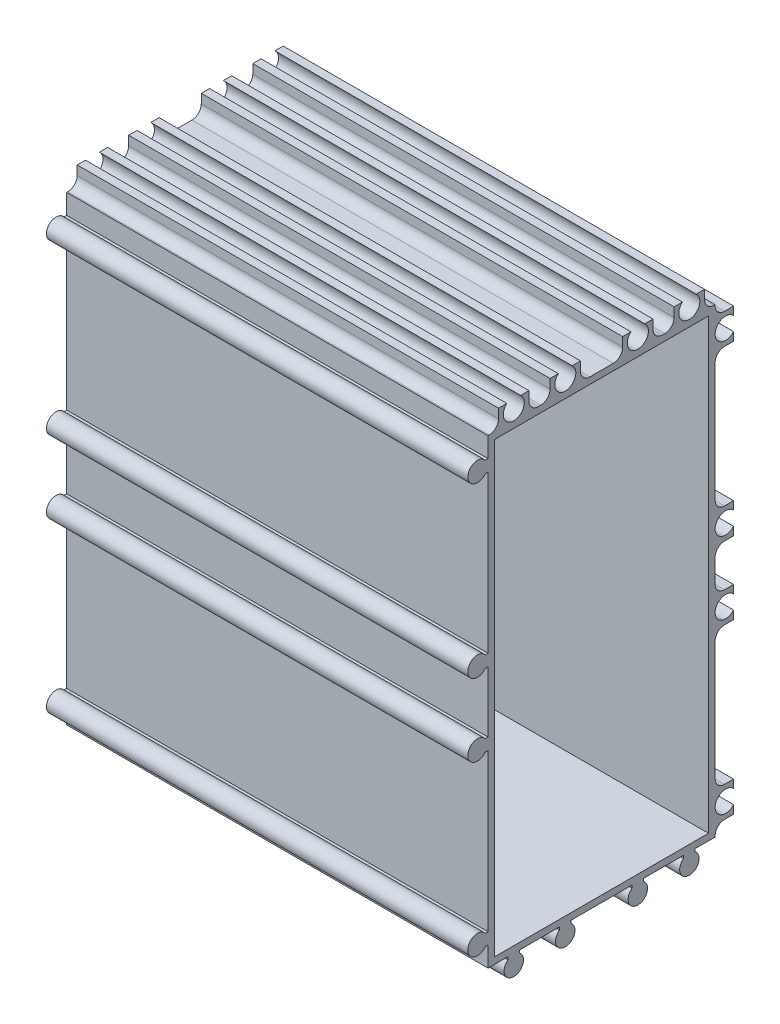
SolidWorks part; units mm, degrees
ref_plane "Спереди" through (0, 0, 0) normal (0, 0, 1) x (1, 0, 0)
ref_plane "Сверху" through (0, 0, 0) normal (0, 1, 0) x (1, 0, 0)
ref_plane "Справа" through (0, 0, 0) normal (1, 0, 0) x (0, 0, -1)
ref_plane "Плоскость4" through (90, 0, 0) normal (1, 0, 0) x (0, 0, -1)
sketch "Эскиз1" plane through (90, 0, 0) normal (1, 0, 0) x (0, 0, -1)
  line L0 (6.75, 225.9062) -> (6.75, 320.75)
  line L1 (6.75, 320.75) -> (-38.0938, 320.75)
  line L2 (-38.0938, 318.25) -> (-37.5, 318.25)
  line L3 (-37.5, 318.25) -> (-37.5, 284.75)
  line L4 (-37.5, 284.75) -> (-38.0938, 284.75)
  line L5 (-38.0938, 282.25) -> (-37.5, 282.25)
  line L6 (-37.5, 282.25) -> (-37.5, 269.25)
  line L7 (-37.5, 269.25) -> (-38.0938, 269.25)
  line L8 (-38.0938, 266.75) -> (-37.5, 266.75)
  line L9 (-37.5, 266.75) -> (-37.5, 233.25)
  line L10 (-37.5, 233.25) -> (-38.0938, 233.25)
  line L11 (-38.0938, 230.75) -> (-37.5, 230.75)
  line L12 (-37.5, 230.75) -> (-37.5, 226.5)
  line L13 (-37.5, 226.5) -> (-33.25, 226.5)
  line L14 (-33.25, 226.5) -> (-33.25, 225.9062)
  line L15 (-30.75, 225.9062) -> (-30.75, 226.5)
  line L16 (-30.75, 226.5) -> (-22.25, 226.5)
  line L17 (-22.25, 226.5) -> (-22.25, 225.9062)
  line L18 (-19.75, 225.9062) -> (-19.75, 226.5)
  line L19 (-19.75, 226.5) -> (-6.75, 226.5)
  line L20 (-6.75, 226.5) -> (-6.75, 225.9062)
  line L21 (-4.25, 225.9062) -> (-4.25, 226.5)
  line L22 (-4.25, 226.5) -> (4.25, 226.5)
  line L23 (4.25, 226.5) -> (4.25, 225.9062)
  arc A0 (-38.0938, 320.75) -> (-38.0938, 318.25) centre (-39.75, 319.5) ccw
  arc A1 (-38.0938, 284.75) -> (-38.0938, 282.25) centre (-39.75, 283.5) ccw
  arc A2 (-38.0938, 269.25) -> (-38.0938, 266.75) centre (-39.75, 268) ccw
  arc A3 (-38.0938, 233.25) -> (-38.0938, 230.75) centre (-39.75, 232) ccw
  arc A4 (-33.25, 225.9062) -> (-30.75, 225.9062) centre (-32, 224.25) ccw
  arc A5 (-22.25, 225.9062) -> (-19.75, 225.9062) centre (-21, 224.25) ccw
  arc A6 (-6.75, 225.9062) -> (-4.25, 225.9062) centre (-5.5, 224.25) ccw
  arc A7 (4.25, 225.9062) -> (6.75, 225.9062) centre (5.5, 224.25) ccw
extrude "Бобышка-Вытянуть1" add sketch "Эскиз1" against normal blind 90
sketch "Эскиз2" plane through (0, 320.75, 0) normal (0, 1, 0) x (-1, 0, 0)
  line L0 (-90, -6.75) -> (-90, 37.5)
  line L1 (-90, 37.5) -> (0, 37.5)
  line L2 (0, 37.5) -> (0, -6.75)
  line L3 (0, -6.75) -> (-90, -6.75)
extrude "Бобышка-Вытянуть2" add sketch "Эскиз2" along normal blind 8.2
sketch "Эскиз3" plane through (0, 0, -6.75) normal (0, 0, -1) x (-1, 0, 0)
  line L0 (-90, 226.5) -> (-90, 328.95)
  line L1 (-90, 328.95) -> (0, 328.95)
  line L2 (0, 328.95) -> (0, 226.5)
  line L3 (0, 226.5) -> (-90, 226.5)
extrude "Бобышка-Вытянуть3" add sketch "Эскиз3" along normal blind 8.2
sketch "Эскиз4" plane through (0, 0, 0) normal (-1, 0, 0) x (0, 0, 1)
  line L0 (24.25, 328.95) -> (24.25, 325)
  line L1 (24.25, 325) -> (28.75, 325)
  line L2 (28.75, 325) -> (28.75, 328.95)
  line L3 (28.75, 328.95) -> (24.25, 328.95)
extrude "Вырез-Вытянуть1" cut sketch "Эскиз4" against normal through all
sketch "Эскиз5" plane through (0, 0, 0) normal (-1, 0, 0) x (0, 0, 1)
  line L0 (37.5, 328.95) -> (35.25, 328.95)
  line L1 (35.25, 328.95) -> (35.25, 325)
  line L2 (35.25, 325) -> (37.5, 325)
  line L3 (37.5, 325) -> (37.5, 328.95)
extrude "Вырез-Вытянуть2" cut sketch "Эскиз5" against normal through all
sketch "Эскиз6" plane through (0, 0, 0) normal (-1, 0, 0) x (0, 0, 1)
  line L0 (-14.95, 226.5) -> (-11, 226.5)
  line L1 (-11, 226.5) -> (-11, 228.75)
  line L2 (-11, 228.75) -> (-14.95, 228.75)
  line L3 (-14.95, 228.75) -> (-14.95, 226.5)
extrude "Вырез-Вытянуть3" cut sketch "Эскиз6" against normal through all
sketch "Эскиз7" plane through (0, 0, 0) normal (-1, 0, 0) x (0, 0, 1)
  line L0 (-14.95, 235.25) -> (-11, 235.25)
  line L1 (-11, 235.25) -> (-11, 264.75)
  line L2 (-11, 264.75) -> (-14.95, 264.75)
  line L3 (-14.95, 264.75) -> (-14.95, 235.25)
extrude "Вырез-Вытянуть4" cut sketch "Эскиз7" against normal through all
sketch "Эскиз8" plane through (0, 0, 0) normal (-1, 0, 0) x (0, 0, 1)
  line L0 (-14.95, 271.25) -> (-11, 271.25)
  line L1 (-11, 271.25) -> (-11, 280.25)
  line L2 (-11, 280.25) -> (-14.95, 280.25)
  line L3 (-14.95, 280.25) -> (-14.95, 271.25)
extrude "Вырез-Вытянуть5" cut sketch "Эскиз8" against normal through all
sketch "Эскиз9" plane through (0, 0, 0) normal (-1, 0, 0) x (0, 0, 1)
  line L0 (-14.95, 286.75) -> (-11, 286.75)
  line L1 (-11, 286.75) -> (-11, 316.25)
  line L2 (-11, 316.25) -> (-14.95, 316.25)
  line L3 (-14.95, 316.25) -> (-14.95, 286.75)
extrude "Вырез-Вытянуть6" cut sketch "Эскиз9" against normal through all
sketch "Эскиз10" plane through (0, 0, 0) normal (-1, 0, 0) x (0, 0, 1)
  line L0 (-14.95, 328.95) -> (-14.95, 322.75)
  line L1 (-14.95, 322.75) -> (-11, 322.75)
  line L2 (-11, 322.75) -> (-11, 328.95)
  line L3 (-11, 328.95) -> (-14.95, 328.95)
extrude "Вырез-Вытянуть7" cut sketch "Эскиз10" against normal through all
sketch "Эскиз11" plane through (0, 0, 0) normal (-1, 0, 0) x (0, 0, 1)
  line L0 (-11, 328.95) -> (-11, 325)
  line L1 (-11, 325) -> (-8.75, 325)
  line L2 (-8.75, 325) -> (-8.75, 328.95)
  line L3 (-8.75, 328.95) -> (-11, 328.95)
extrude "Вырез-Вытянуть8" cut sketch "Эскиз11" against normal through all
sketch "Эскиз12" plane through (0, 0, 0) normal (-1, 0, 0) x (0, 0, 1)
  line L0 (-2.25, 328.95) -> (-2.25, 325)
  line L1 (-2.25, 325) -> (2.25, 325)
  line L2 (2.25, 325) -> (2.25, 328.95)
  line L3 (2.25, 328.95) -> (-2.25, 328.95)
extrude "Вырез-Вытянуть9" cut sketch "Эскиз12" against normal through all
sketch "Эскиз13" plane through (0, 0, 0) normal (-1, 0, 0) x (0, 0, 1)
  line L0 (8.75, 328.95) -> (8.75, 325)
  line L1 (8.75, 325) -> (17.75, 325)
  line L2 (17.75, 325) -> (17.75, 328.95)
  line L3 (17.75, 328.95) -> (8.75, 328.95)
extrude "Вырез-Вытянуть10" cut sketch "Эскиз13" against normal through all
sketch "Эскиз14" plane through (90, 0, 0) normal (1, 0, 0) x (0, 0, -1)
  line L0 (9.6, 323.6) -> (-36.1, 323.6)
  line L1 (-36.1, 323.6) -> (-36.1, 227.9)
  line L2 (-36.1, 227.9) -> (9.6, 227.9)
  line L3 (9.6, 227.9) -> (9.6, 323.6)
extrude "Вырез-Вытянуть11" cut sketch "Эскиз14" against normal blind 86
hole_wizard "Диаметр отверстия Ø2.5 (2.5)1" positions "Эскиз16" profile "Эскиз15" hole size "Ø2.5" standard "Ansi Metric"
sketch "Эскиз16" plane through (90, 0, 0) normal (1, 0, 0) x (0, 0, -1)
  point P0 (-39.75, 232)
  point P1 (-21, 224.25)
  point P2 (-39.75, 283.5)
  point P3 (-5.5, 224.25)
  point P4 (5.5, 224.25)
  point P5 (-39.75, 319.5)
  point P6 (-39.75, 268)
  point P7 (-32, 224.25)
sketch "Эскиз15" plane through (90, 232, 39.75) normal (0, 1, 0) x (0, 0, -1)
  line L0 (0, 0) -> (0, 90)
  line L1 (0, 90) -> (1.25, 90)
  line L2 (1.25, 90) -> (1.25, 0)
  line L5 (1.25, 0) -> (0, 0)
  line L11 (0, -6.35) -> (0, 107.95) construction
  dimension "Диаметр сквозного отверстия" = 2.5
  dimension "Глубина сквозного отверстия" = 90
hole_wizard "Диаметр отверстия Ø4.5 (4.5)1" positions "Эскиз18" profile "Эскиз17" hole size "Ø4.5" standard "Ansi Metric"
sketch "Эскиз18" plane through (0, 0, 0) normal (-1, 0, 0) x (0, 0, 1)
  point P0 (21, 327.25)
  point P1 (32, 327.25)
  point P2 (-13.25, 232)
  point P3 (-13.25, 268)
  point P4 (-13.25, 283.5)
  point P5 (-13.25, 319.5)
  point P6 (-5.5, 327.25)
  point P7 (5.5, 327.25)
sketch "Эскиз17" plane through (0, 327.25, 21) normal (0, 1, 0) x (0, 0, 1)
  line L0 (0, 0) -> (0, 90)
  line L1 (0, 90) -> (2.25, 90)
  line L2 (2.25, 90) -> (2.25, 0)
  line L5 (2.25, 0) -> (0, 0)
  line L11 (0, -6.35) -> (0, 107.95) construction
  dimension "Диаметр сквозного отверстия" = 4.5
  dimension "Глубина сквозного отверстия" = 90
hole_wizard "Диаметр отверстия Ø8.3 (8.3)1" positions "Эскиз20" profile "Эскиз19" hole size "Ø8.3" standard "Ansi Metric"
sketch "Эскиз20" plane through (0, 0, 0) normal (-1, 0, 0) x (0, 0, 1)
  point P0 (13.25, 275.75)
sketch "Эскиз19" plane through (0, 275.75, 13.25) normal (0, 1, 0) x (0, 0, 1)
  line L0 (0, 0) -> (0, 3.2)
  line L1 (0, 3.2) -> (4.15, 3.2)
  line L2 (4.15, 3.2) -> (4.15, 0)
  line L5 (4.15, 0) -> (0, 0)
  line L10 (0, 3.2) -> (-4.15, 3.2) construction
  line L11 (0, -6.35) -> (0, 107.95) construction
  dimension "Диаметр отверстия" = 8.3
  dimension "Глубина отверстия" = 3.2
  dimension "Угол заточки сверла" = 180
sketch "Эскиз21" plane through (0, 0, 0) normal (-1, 0, 0) x (0, 0, 1)
  circle A0 centre (13.25, 275.75) radius 4.15
extrude "Вырез-Вытянуть12" cut sketch "Эскиз21" against normal blind 10
sketch "Эскиз22" plane through (90, 0, 0) normal (1, 0, 0) x (0, 0, -1)
  circle A0 centre (-39.75, 319.5) radius 1.6316
  circle A1 centre (-39.75, 283.5) radius 1.5194
  circle A2 centre (-39.75, 268) radius 1.4876
  circle A3 centre (-39.75, 232) radius 1.5817
  circle A4 centre (-32, 224.25) radius 1.4878
  circle A5 centre (-21, 224.25) radius 1.426
  circle A6 centre (-5.5, 224.25) radius 1.6281
  circle A7 centre (5.5, 224.25) radius 1.5237
extrude "Бобышка-Вытянуть4" add sketch "Эскиз22" against normal blind 90
fillet "Скругление1" radius 2 1 edges at (4, 275.75, -9.6) type face fillet first side face at (47, 275.75, -9.6) second side face at (4, 275.75, 9.1)
fillet "Скругление2" radius 2 1 edges at (4, 275.75, 36.1) type face fillet first side face at (47, 275.75, 36.1) second side face at (4, 275.75, 9.1)
fillet "Скругление3" radius 2 3 edges at (4, 323.6, 13.25) (4.5858, 323.6, -9.0142) (4.5858, 323.6, 35.5142)
fillet "Скругление4" radius 2 3 edges at (4.5858, 227.9, -9.0142) (4, 227.9, 13.25) (4.5858, 227.9, 35.5142)
fillet "Скругление5" radius 2 1 edges at (45, 325, 35.25) type face fillet first side face at (45, 325, 36.375) second side face at (45, 326.975, 35.25)
fillet "Скругление6" radius 2 1 edges at (45, 325, 28.75) type face fillet first side face at (45, 325, 26.5) second side face at (45, 326.975, 28.75)
fillet "Скругление7" radius 2 1 edges at (45, 325, 24.25) type face fillet first side face at (45, 325, 25.5) second side face at (45, 326.975, 24.25)
fillet "Скругление8" radius 2 1 edges at (45, 325, 17.75) type face fillet first side face at (45, 326.975, 17.75) second side face at (45, 325, 13.25)
fillet "Скругление9" radius 2 1 edges at (45, 325, 8.75) type face fillet first side face at (45, 325, 12.25) second side face at (45, 326.975, 8.75)
fillet "Скругление10" radius 2 1 edges at (45, 325, 2.25) type face fillet first side face at (45, 326.975, 2.25) second side face at (45, 325, 0)
fillet "Скругление11" radius 2 1 edges at (45, 325, -2.25) type face fillet first side face at (45, 325, -1) second side face at (45, 326.975, -2.25)
fillet "Скругление12" radius 2 1 edges at (45, 325, -8.75) type face fillet first side face at (45, 325, -9.875) second side face at (45, 326.975, -8.75)
fillet "Скругление13" radius 2 1 edges at (45, 322.75, -11) type face fillet first side face at (45, 323.875, -11) second side face at (45, 322.75, -12.975)
fillet "Скругление14" radius 2 1 edges at (45, 316.25, -11) type face fillet first side face at (45, 316.25, -12.975) second side face at (45, 301.5, -11)
fillet "Скругление15" radius 2 1 edges at (45, 286.75, -11) type face fillet first side face at (45, 300.5, -11) second side face at (45, 286.75, -12.975)
fillet "Скругление16" radius 2 1 edges at (45, 280.25, -11) type face fillet first side face at (45, 275.75, -11) second side face at (45, 280.25, -12.975)
fillet "Скругление17" radius 2 1 edges at (45, 271.25, -11) type face fillet first side face at (45, 274.75, -11) second side face at (45, 271.25, -12.975)
fillet "Скругление18" radius 2 1 edges at (45, 264.75, -11) type face fillet first side face at (45, 264.75, -12.975) second side face at (45, 250, -11)
fillet "Скругление19" radius 2 1 edges at (45, 235.25, -11) type face fillet first side face at (45, 235.25, -12.975) second side face at (45, 249, -11)
fillet "Скругление20" radius 2 1 edges at (45, 228.75, -11) type face fillet first side face at (45, 228.75, -12.975) second side face at (45, 227.625, -11)
